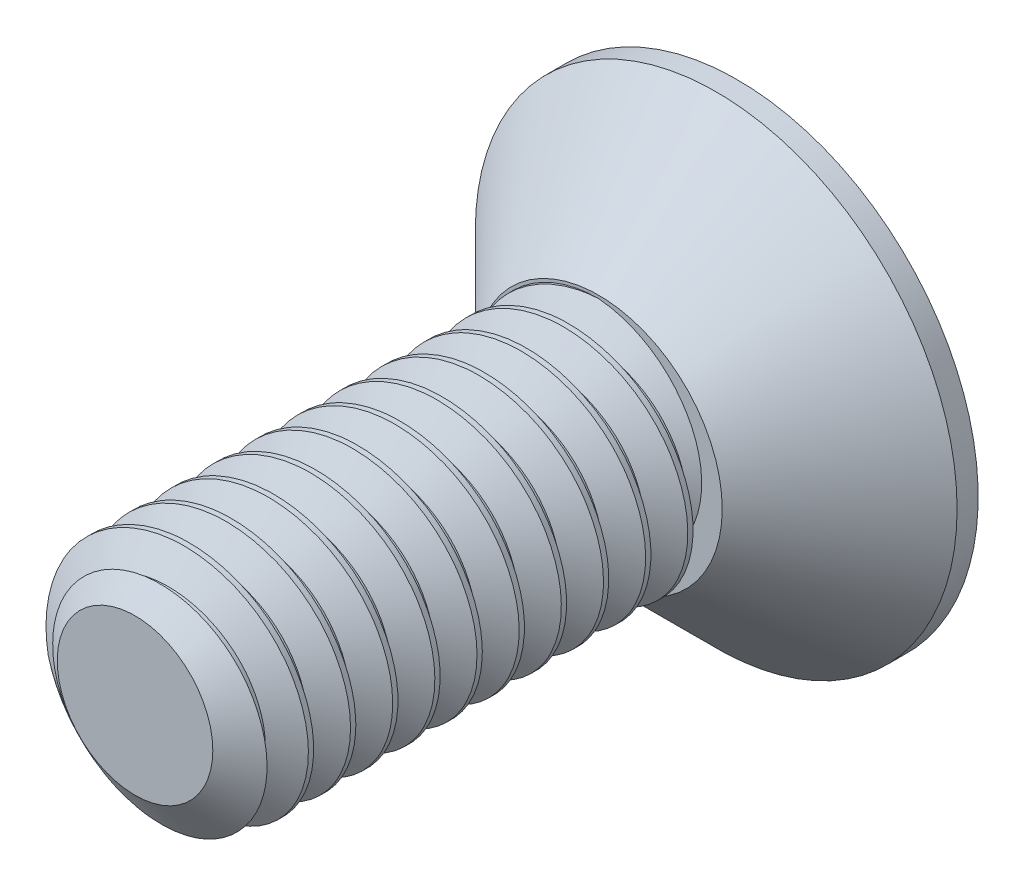
SolidWorks part; units mm, degrees
ref_plane "Front Plane" through (0, 0, 0) normal (0, 0, 1) x (1, 0, 0)
ref_plane "Top Plane" through (0, 0, 0) normal (0, 1, 0) x (1, 0, 0)
ref_plane "Right Plane" through (0, 0, 0) normal (1, 0, 0) x (0, 0, -1)
sketch "Sketch1" plane through (0, 0, 0) normal (0, 0, 1) x (1, 0, 0)
  circle A0 centre (0, 0) radius 2
  dimension "OD" = 4
extrude "Extrude1" add sketch "Sketch1" against normal blind 10
sketch "Sketch2" plane through (0, 0, 0) normal (0, 0, 1) x (1, 0, 0)
  circle A0 centre (0, 0) radius 2 construction
  circle A1 centre (0, 0) radius 2
curve "Helix/Spiral1" pitch 0.7 height 10.7 radius 2 centre (0, 0, 0) axis (0, 0, -1) start towards (0, 1, 0) parameters "pitch"=0.7
sketch "Sketch3" plane through (0, 0, 0) normal (1, 0, 0) x (0, 0, -1)
  line L0 (-0.6125, 2) -> (-0.35, 1.5453)
  line L1 (-0.35, 1.5453) -> (-0.2625, 1.5453)
  line L2 (-0.2625, 1.5453) -> (0, 2)
  line L3 (-0.6125, 2) -> (0, 2)
  line L4 (-0.3062, 2) -> (-0.3062, 1.5453) construction
  line L5 (-0.4812, 1.7727) -> (-0.1312, 1.7727) construction
  line L6 (0, 2) -> (0, -2) construction
  dimension "D1" = 0.0875
  dimension "D2" = 0.35
  dimension "D3" = 60
sweep "Cut-Sweep1" cut profiles "Sketch3" path "Helix/Spiral1"
sketch "Sketch4" plane through (0, 0, 0) normal (1, 0, 0) x (0, 0, -1)
  line L0 (0.4962, 2) -> (0, 1.2913)
  line L1 (0, 1.2913) -> (0, 2)
  line L2 (0.4962, 2) -> (0, 2)
  line L3 (-0.6125, 2) -> (0, 2) construction
  line L4 (0, 0) -> (7.0209, 0) construction
  dimension "D1" = 55
  dimension "D2" = 0.254
revolve "Cut-Revolve1" cut sketch "Sketch4" angle 360 about L4
sketch "Sketch5" plane through (0, 0, 0) normal (1, 0, 0) x (0, 0, -1)
  line L0 (10, 0.3311) -> (10, 1.814) construction
  line L1 (10, 2.05) -> (28.1906, 2.05)
  line L2 (10, 2.05) -> (10, 0)
  line L3 (10, 0) -> (28, 0)
  line L4 (28, 1.7198) -> (28, 0)
  line L5 (28.1906, 2.05) -> (28, 1.7198)
  line L6 (0, 0) -> (9.9695, 0) construction
  point P3 (28, 2.05)
  point P10 (28, 2.05)
  dimension "D1" = 0.3302
  dimension "Thread min" = 28
  dimension "D2" = 0.05
  dimension "D3" = 30
revolve "partially thread" [suppressed] add sketch "Sketch5" angle 360 about L6
sketch "Sketch6" plane through (0, 0, -10) normal (0, 0, -1) x (-1, 0, 0)
  circle A0 centre (0, 0) radius 4
  dimension "head dia" = 8
extrude "Extrude2" add sketch "Sketch6" against normal blind 2.3
sketch "Sketch10" plane through (0, 0, 0) normal (1, 0, 0) x (0, 0, -1)
  line L0 (9.65, -4) -> (7.7, -2.05)
  line L1 (7.7, -2.05) -> (7.7, -4)
  line L2 (9.65, -4) -> (7.7, -4)
  line L3 (0, 0) -> (7.7, 0) construction
  line L4 (7.7, 4) -> (7.7, -4) construction
  line L8 (7.7, 4) -> (7.7, -4) construction
  line L9 (7.7, 2.05) -> (7.7, -2.05) construction
  dimension "D1" = 45
  dimension "D2" = 0.05
revolve "Cut-Revolve2" cut sketch "Sketch10" angle 360 about L3
sketch "Sketch7" plane through (0, 0, -10) normal (0, 0, 1) x (1, 0, 0)
  line L1 (0, 1.4434) -> (-1.25, 0.7217)
  line L2 (-1.25, 0.7217) -> (-1.25, -0.7217)
  line L3 (-1.25, -0.7217) -> (0, -1.4434)
  line L4 (0, -1.4434) -> (1.25, -0.7217)
  line L5 (1.25, -0.7217) -> (1.25, 0.7217)
  line L6 (1.25, 0.7217) -> (0, 1.4434)
  circle A0 centre (0, 0) radius 1.25 construction
  dimension "hex dia" = 2.5
extrude "Cut-Extrude1" cut sketch "Sketch7" along normal blind 1.875
sketch "Sketch8" plane through (0, 0, -10) normal (0, 0, 1) x (1, 0, 0)
  circle A0 centre (0, 0) radius 1.4434
extrude "Cut-Extrude2" cut sketch "Sketch8" along normal through all draft 45
sketch "Sketch9" plane through (0, 0, 0) normal (1, 0, 0) x (0, 0, -1)
  line L0 (0, 2) -> (0, -2) construction
  line L1 (3.85, 2) -> (3.85, -2) construction
  line L2 (7.7, 2) -> (7.7, -2) construction
  line L3 (7.7, -2.05) -> (7.7, -4) construction
  dimension "D1" = 3.85
equation "\"D3@Helix/Spiral1\" = \"screw length@Extrude1\"+\"pitch@Helix/Spiral1\""
equation "\"D1@Sketch3\" = \"pitch@Helix/Spiral1\"*.125"
equation "\"D2@Sketch3\" = \"pitch@Helix/Spiral1\"*.5"
equation "\"D1@Cut-Extrude1\" = \"hex dia@Sketch7\"*.75"
equation "\"D1@Sketch9\" = \"pitch@Helix/Spiral1\"*5.5"
equation "\"D2@Sketch10\" = \"D2@Sketch5\""
